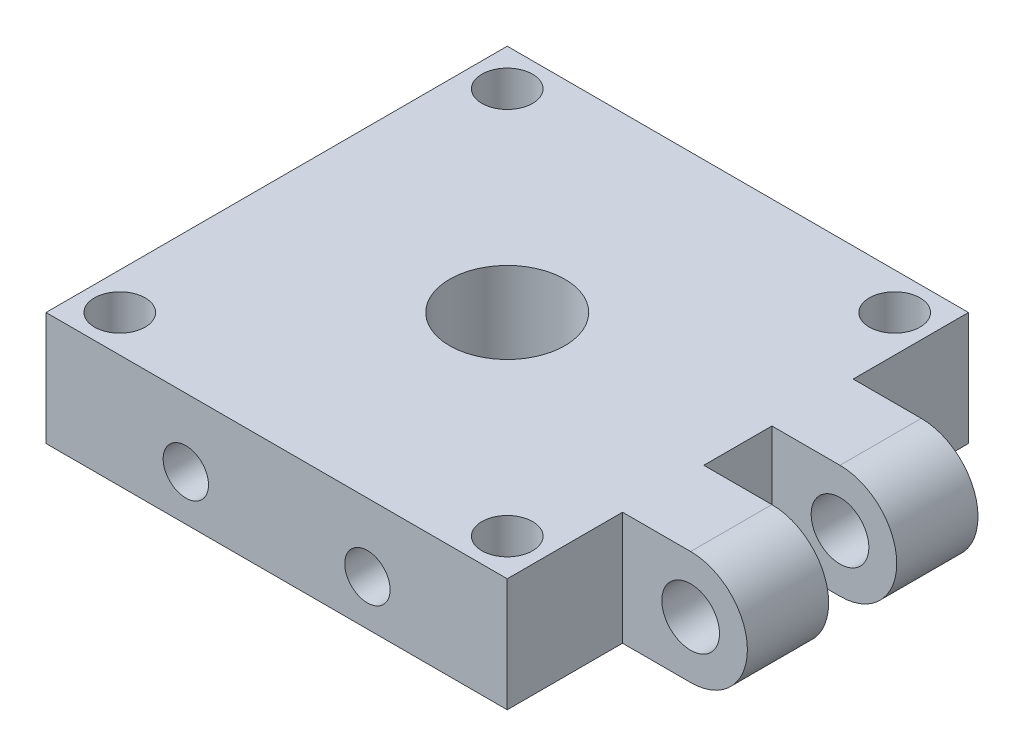
SolidWorks part; units mm, degrees
ref_plane "Front Plane" through (0, 0, 0) normal (0, 0, 1) x (1, 0, 0)
ref_plane "Top Plane" through (0, 0, 0) normal (0, 1, 0) x (1, 0, 0)
ref_plane "Right Plane" through (0, 0, 0) normal (1, 0, 0) x (0, 0, -1)
sketch "Sketch1" plane through (0, 0, 0) normal (0, 1, 0) x (1, 0, 0)
  line L1 (-25.4, -25.4) -> (25.4, -25.4)
  line L2 (-25.4, -25.4) -> (-25.4, 25.4)
  line L3 (-25.4, 25.4) -> (25.4, 25.4)
  line L4 (25.4, -25.4) -> (25.4, 25.4)
  line L5 (-25.4, -25.4) -> (25.4, 25.4) construction
  line L6 (-25.4, 25.4) -> (25.4, -25.4) construction
  circle A0 centre (-21.336, -21.336) radius 2.794
  circle A1 centre (21.336, -21.336) radius 2.794
  circle A2 centre (21.336, 21.336) radius 2.794
  circle A3 centre (-21.336, 21.336) radius 2.794
  circle A4 centre (0, 0) radius 6.35
  point P0 (0, 0)
  dimension "D3" = 5.588
  dimension "D4" = 12.7
  dimension "D1" = 50.8
  dimension "D2" = 21.336
extrude "Boss-Extrude1" add sketch "Sketch1" along normal blind 12.5
sketch "Sketch4" plane through (0, 0, 0) normal (0, 0, 1) x (1, 0, 0)
  line L0 (25.4, 12.5) -> (40.4, 12.5) construction
  line L1 (25.4, 0) -> (32.9, 0)
  line L2 (25.4, 0) -> (25.4, 12.5)
  line L3 (25.4, 12.5) -> (32.9, 12.5)
  arc A0 (32.9, 12.5) -> (32.9, 0) centre (32.9, 6.25) cw
  circle A1 centre (32.9, 6.25) radius 3.175
  point P9 (0, 0)
  point P10 (0, 0)
  point P11 (0, 0)
  point P12 (32.9, 12.5)
  point P13 (0, 0)
  dimension "D1" = 6.35
  dimension "D2" = 7.5
extrude "Boss-Extrude2" add sketch "Sketch4" along normal mid plane 25.4
sketch "Sketch5" plane through (0, 12.5, 0) normal (0, 1, 0) x (1, 0, 0)
  line L9 (39.15, -12.7) -> (39.15, 12.7) construction
  line L10 (25.4, 3.75) -> (39.15, 3.75)
  line L11 (25.4, 3.75) -> (25.4, -3.75)
  line L12 (25.4, -3.75) -> (39.15, -3.75)
  line L13 (39.15, 3.75) -> (39.15, -3.75)
  line L14 (25.4, 3.75) -> (39.15, -3.75) construction
  line L15 (25.4, -3.75) -> (39.15, 3.75) construction
  line L16 (25.4, -25.4) -> (25.4, -12.7) construction
  point P0 (32.275, 0)
  point P10 (0, 0)
  dimension "D1" = 7.5
extrude "Cut-Extrude2" cut sketch "Sketch5" against normal through all
sketch "Sketch14" plane through (0, 0, 25.4) normal (0, 0, 1) x (1, 0, 0)
  line L0 (-10, 5) -> (10, 5) construction
  line L1 (-25.4, 0) -> (25.4, 0) construction
  circle A0 centre (-10, 5) radius 2.5
  circle A1 centre (10, 5) radius 2.5
  point P6 (0, 5)
  dimension "D1" = 5
  dimension "D2" = 20
  dimension "D3" = 5
extrude "Cut-Extrude7" cut sketch "Sketch14" against normal blind 20
sketch "Sketch15" plane through (-25.4, 0, 0) normal (-1, 0, 0) x (0, 0, 1)
  line L0 (-10, 5) -> (10, 5) construction
  line L1 (-25.4, 0) -> (25.4, 0) construction
  circle A0 centre (-10, 5) radius 2.5
  circle A1 centre (10, 5) radius 2.5
  point P4 (0, 5)
  dimension "D1" = 5
  dimension "D2" = 20
  dimension "D3" = 5
extrude "Cut-Extrude8" cut sketch "Sketch15" against normal blind 20
